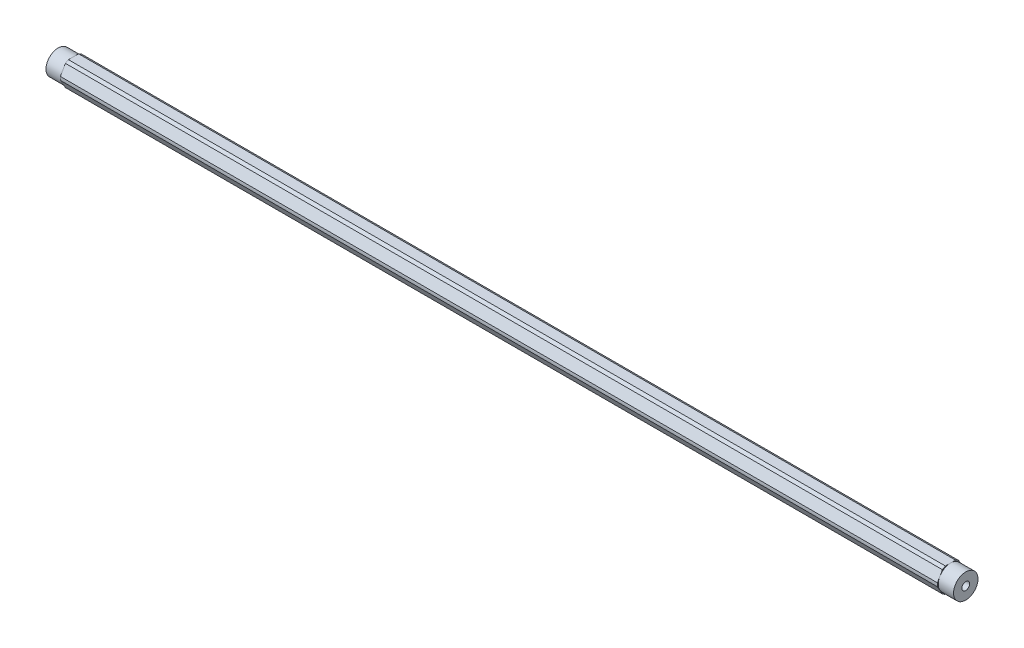
SolidWorks part; units mm, degrees
material "7075-T6 (SN)"
ref_plane "Front Plane" through (0, 0, 0) normal (0, 0, 1) x (1, 0, 0)
ref_plane "Top Plane" through (0, 0, 0) normal (0, 1, 0) x (1, 0, 0)
ref_plane "Right Plane" through (0, 0, 0) normal (1, 0, 0) x (0, 0, -1)
sketch "Sketch1" plane through (0, 0, 0) normal (1, 0, 0) x (0, 0, -1)
  line L1 (3.6662, 6.35) -> (-3.6662, 6.35)
  line L2 (-3.6662, 6.35) -> (-7.3323, 0)
  line L3 (-7.3323, 0) -> (-3.6662, -6.35)
  line L4 (-3.6662, -6.35) -> (3.6662, -6.35)
  line L5 (3.6662, -6.35) -> (7.3323, 0)
  line L6 (7.3323, 0) -> (3.6662, 6.35)
  circle A0 centre (0, 0) radius 2.0193
  circle A1 centre (0, 0) radius 6.875
  circle A2 centre (0, 0) radius 6.35 construction
  dimension "D1" = 13.75
  dimension "D2" = 4.0386
  dimension "D3" = 12.7
extrude "Boss-Extrude1" add sketch "Sketch1" along normal mid plane 471.4875 contours L6 A1 L1 L2 L3 L4 L5 A0 region at (0, 5.7918, -3.3439)
sketch "Sketch2" plane through (235.7438, 0, 0) normal (1, 0, 0) x (0, 0, -1)
  circle A0 centre (0, 0) radius 6.35
  dimension "D1" = 12.7
extrude "Cut-Extrude-Thin1" cut sketch "Sketch2" against normal blind 7.9375 thin thin type one direction wall 2.54
mirror "Mirror1" about plane through (0, 0, 0) normal (1, 0, 0) of "Cut-Extrude-Thin1"
equation "\"D1@Sketch1\"=13.75mm"
